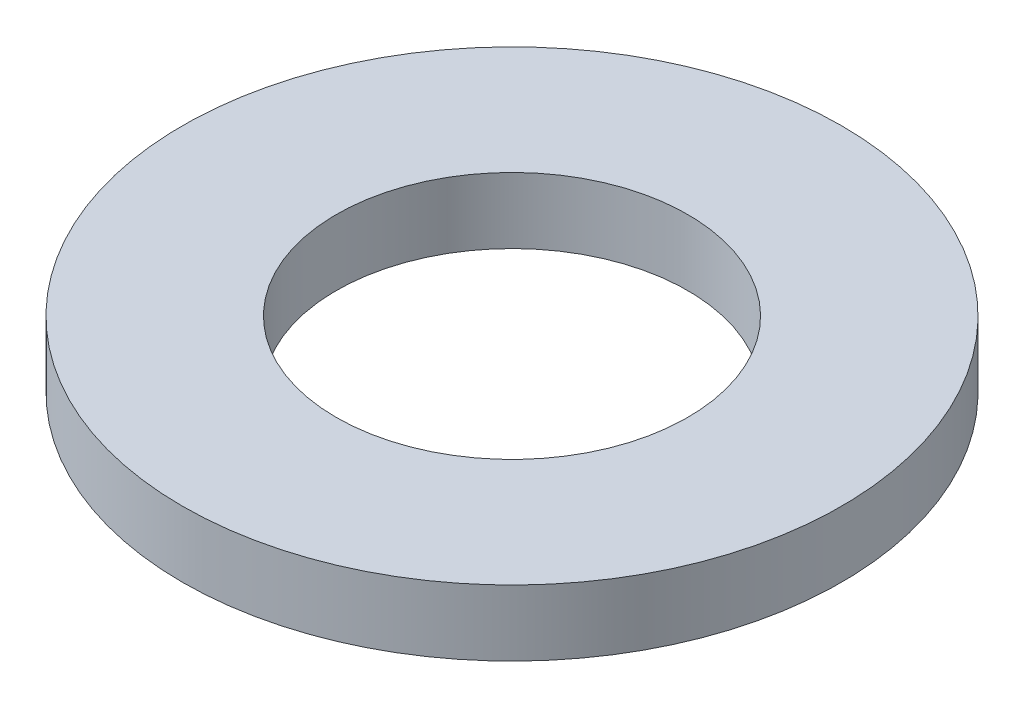
SolidWorks part; units mm, degrees
ref_plane "Front Plane" through (0, 0, 0) normal (0, 0, 1) x (1, 0, 0)
ref_plane "Top Plane" through (0, 0, 0) normal (0, 1, 0) x (1, 0, 0)
ref_plane "Right Plane" through (0, 0, 0) normal (1, 0, 0) x (0, 0, -1)
sketch "Sketch1" plane through (0, 0, 0) normal (0, 1, 0) x (1, 0, 0)
  circle A0 centre (0, 0) radius 8
  circle A1 centre (0, 0) radius 15
  dimension "D1" = 16
  dimension "D2" = 30
extrude "Boss-Extrude1" add sketch "Sketch1" along normal blind 3
